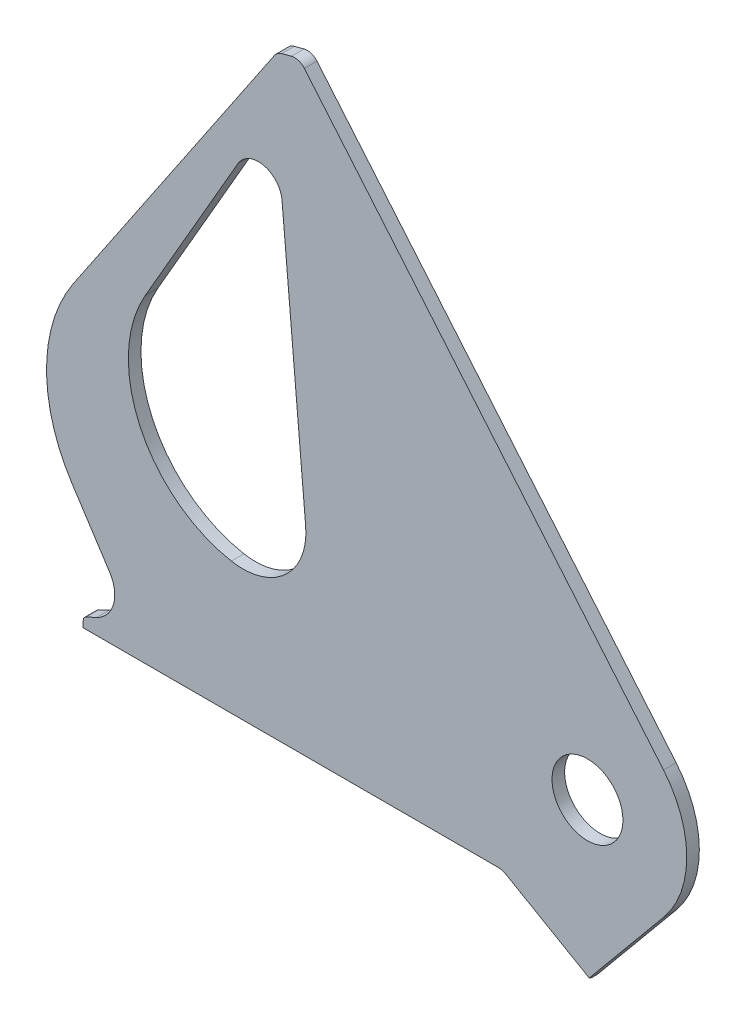
SolidWorks part; units mm, degrees
ref_plane "Plane1" through (0, 0, 0) normal (0, 0, 1) x (1, 0, 0)
ref_plane "Plane2" through (0, 0, 0) normal (0, 1, 0) x (1, 0, 0)
ref_plane "Plane3" through (0, 0, 0) normal (1, 0, 0) x (0, 0, -1)
sketch "Sketch1" plane through (0, 0, 0) normal (0, 0, 1) x (1, 0, 0)
  line L0 (-317, -72.5) -> (-56.8038, -72.5)
  line L1 (-55.3038, -72.9019) -> (-5.6007, -101.5981)
  line L2 (-1.7904, -100.9139) -> (48.5145, -40.1913)
  line L3 (48.2608, 40.4956) -> (-179.6778, 312.1423)
  line L4 (-320, -69.5) -> (-320, -61.4126)
  line L5 (-318.2679, -58.6937) -> (-311.5476, -55.56)
  line L6 (-303.2266, -26.5411) -> (-327.1562, 10.3073)
  line L7 (-187.8767, 314.7274) -> (-194.0647, 313.0694)
  line L8 (-198.6264, 309.8155) -> (-326.1929, 120.6905)
  line L9 (-193.8537, 232.6071) -> (-178.8388, 60.9862)
  line L10 (-280.6611, 136.8268) -> (-221.787, 238.7998)
  line L11 (0, 0) -> (0, 352.5158) construction
  circle A0 centre (0, 0) radius 22.5
  arc A1 (48.5145, -40.1913) -> (48.2608, 40.4956) centre (0, 0) ccw
  arc A2 (-311.5476, -55.56) -> (-303.2266, -26.5411) centre (-320, -37.4338) ccw
  arc A3 (-178.8388, 60.9862) -> (-225.9941, 18.1732) centre (-218.6866, 57.5) cw
  arc A4 (-225.9941, 18.1732) -> (-280.6611, 136.8268) centre (-211.379, 96.8268) cw
  arc A5 (-179.6778, 312.1423) -> (-187.8767, 314.7274) centre (-185.8062, 307) ccw
  arc A6 (-5.6007, -101.5981) -> (-1.7904, -100.9139) centre (-4.1007, -99) ccw
  arc A7 (-194.0647, 313.0694) -> (-198.6264, 309.8155) centre (-191.9941, 305.3419) ccw
  arc A8 (-326.1929, 120.6905) -> (-327.1562, 10.3073) centre (-243.2891, 64.7712) ccw
  arc A9 (-56.8038, -72.5) -> (-55.3038, -72.9019) centre (-56.8038, -75.5) cw
  arc A10 (-317, -72.5) -> (-320, -69.5) centre (-317, -69.5) cw
  arc A11 (-320, -61.4126) -> (-318.2679, -58.6937) centre (-317, -61.4126) cw
  arc A12 (-221.787, 238.7998) -> (-193.8537, 232.6071) centre (-208.7966, 231.2998) cw
  point P26 (-182.9538, 316.0465)
  point P36 (-56, -72.5)
  point P39 (-320, -72.5)
  point P42 (-320, -59.5014)
  point P44 (-198, 280)
  point P45 (-196.9538, 312.2952)
  dimension "D4" = 63
  dimension "D7" = 33
  dimension "D8" = 40
  dimension "D9" = 20
  dimension "D16" = 90
  dimension "D17" = 8
  dimension "D18" = 315
  dimension "D21" = 20
  dimension "D23" = 3
  dimension "D24" = 29.5
  dimension "D25" = 45
  dimension "D26" = 100
  dimension "D27" = 3
  dimension "D28" = 3
  dimension "D15" = 80
  dimension "D19" = 15
  dimension "D1" = 30
  dimension "D3" = 72.5
  dimension "D5" = 50
  dimension "D6" = 65
  dimension "D10" = 12.9986
  dimension "D11" = 25
  dimension "D12" = 320
  dimension "D13" = 5
  dimension "D14" = 34
  dimension "D20" = 280
  dimension "D22" = 14
  dimension "D29" = 56
  dimension "D30" = 20.5105
  dimension "D31" = 4
  dimension "D32" = 198
extrude "Extrude1" add sketch "Sketch1" along normal blind 8
chamfer "7 x 45 gr skærpning - Venstre" distance 7 angle 45 3 edges at (-30.4523, -87.25, 8) (-56.0274, -72.6022, 8) (-186.9019, -72.5, 8)
chamfer "7 x 45 gr skærpning - Højre" [suppressed] distance 7 angle 45
